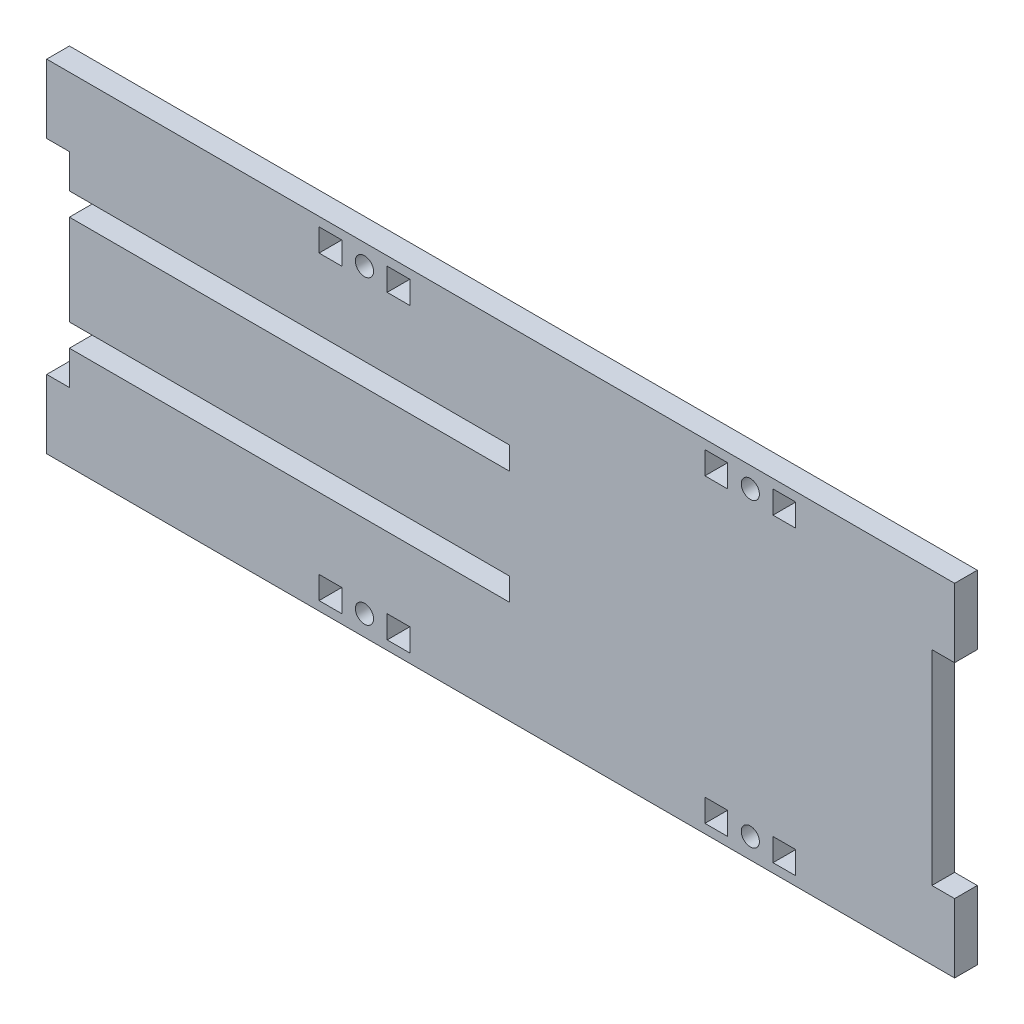
SolidWorks part; units mm, degrees
ref_plane "Plan de face" through (0, 0, 0) normal (0, 0, 1) x (1, 0, 0)
ref_plane "Plan de dessus" through (0, 0, 0) normal (0, 1, 0) x (1, 0, 0)
ref_plane "Plan de droite" through (0, 0, 0) normal (1, 0, 0) x (0, 0, -1)
sketch "Esquisse1" plane through (0, 0, 0) normal (0, 0, 1) x (1, 0, 0)
  line L0 (0, 0) -> (150, 0) construction
  line L1 (0, 37.65) -> (150, 37.65)
  line L2 (150, 37.65) -> (150, -37.65) construction
  line L3 (0, 37.65) -> (0, -37.65) construction
  line L4 (0, -37.65) -> (150, -37.65)
  line L5 (0, 37.65) -> (-50, 37.65)
  line L6 (150, 37.65) -> (150, 22.5)
  line L8 (-45, 10) -> (0, 10)
  line L9 (0, 10) -> (52, 10)
  line L10 (52, 10) -> (-45, 10)
  line L13 (-45, -10) -> (52, -10)
  line L14 (52, -10) -> (52, -15)
  line L15 (52, -15) -> (-50, -15) construction
  line L16 (-50, -15) -> (-50, -37.65) construction
  line L17 (150, 22.5) -> (145, 22.5)
  line L18 (-50, -37.65) -> (0, -37.65)
  line L19 (-45, 10) -> (-45, -10)
  line L20 (52, 10) -> (52, 15)
  line L21 (52, 15) -> (-50, 15) construction
  line L22 (-50, 15) -> (-50, 37.65) construction
  line L23 (145, 22.5) -> (145, -22.5)
  line L24 (145, -22.5) -> (150, -22.5)
  line L25 (150, -22.5) -> (150, -37.65)
  line L26 (-50, 37.65) -> (-50, 22.5)
  line L27 (-50, 22.5) -> (-45, 22.5)
  line L28 (-45, 22.5) -> (-45, 15)
  line L29 (-45, 15) -> (52, 15)
  line L30 (-45, -15) -> (52, -15)
  line L31 (-45, -22.5) -> (-45, -15)
  line L32 (-50, -22.5) -> (-45, -22.5)
  line L33 (-50, -37.65) -> (-50, -22.5)
  line B0 (100, 33.15) -> (110, 33.15) construction
  line B1 (100, 35.65) -> (95, 35.65)
  line B2 (100, 35.65) -> (100, 30.65)
  line B3 (100, 30.65) -> (95, 30.65)
  line B4 (95, 35.65) -> (95, 30.65)
  line B5 (110, 35.65) -> (115, 35.65)
  line B6 (110, 35.65) -> (110, 30.65)
  line B7 (110, 30.65) -> (115, 30.65)
  line B8 (115, 35.65) -> (115, 30.65)
  line B9 (105, 33.15) -> (105, 40.1224) construction
  circle B10 centre (105, 33.15) radius 2
  line B11 (100, -33.15) -> (110, -33.15) construction
  line B12 (100, -35.65) -> (95, -35.65)
  line B13 (100, -35.65) -> (100, -30.65)
  line B14 (100, -30.65) -> (95, -30.65)
  line B15 (95, -35.65) -> (95, -30.65)
  line B16 (110, -35.65) -> (115, -35.65)
  line B17 (110, -35.65) -> (110, -30.65)
  line B18 (110, -30.65) -> (115, -30.65)
  line B19 (115, -35.65) -> (115, -30.65)
  line B20 (105, -33.15) -> (105, -40.1224) construction
  circle B21 centre (105, -33.15) radius 2
  line B22 (15, 33.15) -> (25, 33.15) construction
  line B23 (15, 35.65) -> (10, 35.65)
  line B24 (15, 35.65) -> (15, 30.65)
  line B25 (15, 30.65) -> (10, 30.65)
  line B26 (10, 35.65) -> (10, 30.65)
  line B27 (25, 35.65) -> (30, 35.65)
  line B28 (25, 35.65) -> (25, 30.65)
  line B29 (25, 30.65) -> (30, 30.65)
  line B30 (30, 35.65) -> (30, 30.65)
  line B31 (20, 33.15) -> (20, 40.1224) construction
  circle B32 centre (20, 33.15) radius 2
  line B33 (15, -33.15) -> (25, -33.15) construction
  line B34 (15, -35.65) -> (10, -35.65)
  line B35 (15, -35.65) -> (15, -30.65)
  line B36 (15, -30.65) -> (10, -30.65)
  line B37 (10, -35.65) -> (10, -30.65)
  line B38 (25, -35.65) -> (30, -35.65)
  line B39 (25, -35.65) -> (25, -30.65)
  line B40 (25, -30.65) -> (30, -30.65)
  line B41 (30, -35.65) -> (30, -30.65)
  line B42 (20, -33.15) -> (20, -40.1224) construction
  circle B43 centre (20, -33.15) radius 2
  dimension "D1" = 45
  dimension "D2" = 200
  dimension "D3" = 2
  dimension "D4" = 102
  dimension "D5" = 33.15
  dimension "D6" = 5
  dimension "D7" = 50
  dimension "D8" = 20
  dimension "D9" = 20
  dimension "D10" = 85
  dimension "D11" = 98
  dimension "D12" = 5
  dimension "D13" = 30
  dimension "D14" = 5
  dimension "D15" = 5
  dimension "D16" = 7.5
sketch_block_instance "Trou M4 plots 5mm-1"
sketch_block "Trou M4 plots 5mm" parameters "D2"=4, "D1"=5, "D3"=5, "D4"=10
sketch_block_instance "Trou M4 plots 5mm-5"
sketch_block_instance "Trou M4 plots 5mm-6"
sketch_block_instance "Trou M4 plots 5mm-7"
extrude "Boss.-Extru.1" add sketch "Esquisse1" along normal blind 5 contours L22 L21 L20 L9 L8 L19 L13 L14 L15 L16 L18 L4 L2 L1 L5 B34 B37 B36 B35 B27 B30 B29 B28 B21 B19 B16 B17 B18 B10 B4 B1 B2 B3 B5 B8 B7 B6 B12 B15 B14 B13 B26 region at (53.135, 0, 0)
